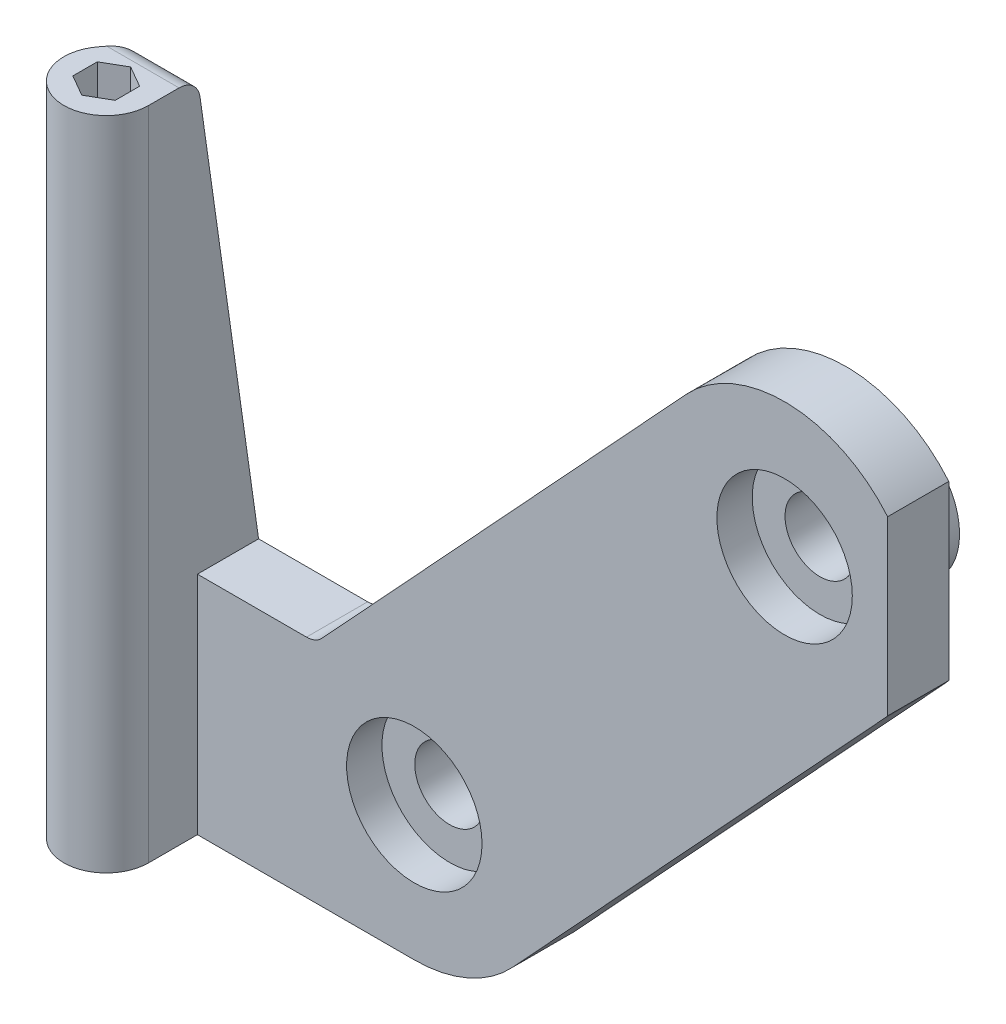
SolidWorks part; units mm, degrees
material "6061-T6 (SS)"
ref_plane "Front Plane" through (0, 0, 0) normal (0, 0, 1) x (1, 0, 0)
ref_plane "Top Plane" through (0, 0, 0) normal (0, 1, 0) x (1, 0, 0)
ref_plane "Right Plane" through (0, 0, 0) normal (1, 0, 0) x (0, 0, -1)
ref_axis "Axis1" through (0, 0, 55) along (0, 0, -1)
sketch "Sketch1" plane through (0, 0, 0) normal (0, 0, 1) x (1, 0, 0)
  line L0 (0, 0) -> (0, 18.9) construction
  line L1 (0, 18.9) -> (17.5, 18.9) construction
  line L2 (4.6594, -4.3142) -> (22.1594, 14.5858)
  line L3 (-4.6594, 4.3142) -> (12.8406, 23.2142)
  arc A0 (-4.6594, 4.3142) -> (4.6594, -4.3142) centre (0, 0) ccw
  arc A1 (22.1594, 14.5858) -> (12.8406, 23.2142) centre (17.5, 18.9) ccw
  dimension "D1" = 12.7
  dimension "D2" = 17.5
  dimension "D3" = 18.9
extrude "Boss-Extrude1" add sketch "Sketch1" along normal mid plane 2.89
sketch "Sketch2" plane through (0, 0, 1.445) normal (0, 0, 1) x (1, 0, 0)
  circle A0 centre (0, 0) radius 3.2
  circle A1 centre (17.5, 18.9) radius 3.2
  dimension "D1" = 6.4
extrude "Cut-Extrude1" cut sketch "Sketch2" against normal blind 1.67
sketch "Sketch3" plane through (0, 0, -0.225) normal (0, 0, 1) x (1, 0, 0)
  circle A0 centre (0, 0) radius 3.2 construction
  circle A1 centre (0, 0) radius 3.2
  circle A2 centre (17.5, 18.9) radius 3.2 construction
  circle A3 centre (17.5, 18.9) radius 3.2
extrude "Boss-Extrude2" add sketch "Sketch3" against normal blind 3.4
sketch "Sketch5" plane through (0, 0, 1.445) normal (0, 0, 1) x (1, 0, 0)
  line L0 (22.37, 14.825) -> (22.37, 22.975)
  arc A0 (22.1594, 14.5858) -> (12.8406, 23.2142) centre (17.5, 18.9) ccw construction
  arc A1 (22.37, 14.825) -> (22.37, 22.975) centre (17.5, 18.9) ccw
  point P7 (22.37, 14.8132)
  point P10 (0, 0)
  point P11 (0, 0)
  point P12 (0, 0)
  dimension "D1" = 4.87
extrude "Cut-Extrude3" cut sketch "Sketch5" against normal through all
sketch "Sketch6" plane through (0, 0, -0.225) normal (0, 0, 1) x (1, 0, 0)
  circle A0 centre (0, 0) radius 1.65
  circle A1 centre (17.5, 18.9) radius 1.65
  dimension "D1" = 3.3
extrude "Cut-Extrude4" cut sketch "Sketch6" against normal through all
sketch "Sketch7" plane through (0, 0, 1.445) normal (0, 0, 1) x (1, 0, 0)
  line L0 (-4.6594, 4.3142) -> (-13, 4.3142)
  line L1 (-13, 4.3142) -> (-13, -6.35)
  line L2 (0, -6.35) -> (-13, -6.35)
  line L6 (22.37, 14.825) -> (22.37, 22.975)
  line L7 (12.8406, 23.2142) -> (-4.6594, 4.3142)
  line L8 (4.6594, -4.3142) -> (22.1594, 14.5858)
  arc A0 (-4.6594, 4.3142) -> (4.6594, -4.3142) centre (0, 0) ccw construction
  arc A4 (22.37, 22.975) -> (12.8406, 23.2142) centre (17.5, 18.9) ccw
  arc A5 (-4.6594, 4.3142) -> (4.6594, -4.3142) centre (0, 0) ccw
  arc A6 (22.1594, 14.5858) -> (22.37, 14.825) centre (17.5, 18.9) ccw
  arc A8 (-4.6594, 4.3142) -> (0, -6.35) centre (0, 0) ccw
  point P3 (-21.4195, -6.1651)
  point P4 (0, -6.35)
  point P6 (-21.4931, -6.509)
  point P12 (0, 0)
  dimension "D1" = 13
  dimension "D2" = 0
extrude "Boss-Extrude3" add sketch "Sketch7" against normal up to surface (2.89 mm away) up to face at (20.7, 18.9, -1.445)
sketch "Sketch8" plane through (0, -6.35, 0) normal (0, -1, 0) x (1, 0, 0)
  line L0 (-13, -1.445) -> (-13, 1.445) construction
  line L1 (-11.5, 3.322) -> (-11.5, 4.188) construction
  line L2 (-11.5, 4.188) -> (-12.25, 4.621) construction
  line L3 (-12.25, 4.621) -> (-13, 4.188) construction
  line L4 (-13, 4.188) -> (-13, 3.322) construction
  line L5 (-13, 3.322) -> (-12.25, 2.889) construction
  line L6 (-12.25, 2.889) -> (-11.5, 3.322) construction
  line L7 (-13, 1.445) -> (0, 1.445) construction
  line L8 (-13, 1.445) -> (-13.8378, 2.5389)
  line L9 (-10.25, 3.755) -> (-10.25, 1.445)
  line L11 (-12.25, 2.6003) -> (-11.25, 3.1776)
  line L12 (-11.25, 3.1776) -> (-11.25, 4.3324)
  line L13 (-11.25, 4.3324) -> (-12.25, 4.9097)
  line L14 (-12.25, 4.9097) -> (-13.25, 4.3324)
  line L15 (-13.25, 4.3324) -> (-13.25, 3.1776)
  line L16 (-13.25, 3.1776) -> (-12.25, 2.6003)
  circle A0 centre (-12.25, 3.755) radius 0.75 construction
  circle A1 centre (-12.25, 3.755) radius 1 construction
  arc A2 (-10.25, 3.755) -> (-13.8378, 2.5389) centre (-12.25, 3.755) ccw
  circle A3 centre (-12.25, 3.755) radius 2 construction
  circle A4 centre (-12.25, 3.755) radius 1 construction
  line M10 (0, 1.445) -> (-13, 1.445)
  dimension "D1" = 1.5
  dimension "D5" = 2
  dimension "D3" = 2.31
  dimension "D4" = 1
extrude "Boss-Extrude4" add sketch "Sketch8" against normal blind 31 contours L9 A2 L8 A1 M10 region at (-13.3722, -6.35, 2.0277)
sketch "Sketch10" plane through (-13, 0, 0) normal (-1, 0, 0) x (0, 0, 1)
  line L0 (-1.445, 4.3142) -> (1.445, 24.65)
  line L1 (1.445, 24.65) -> (1.445, 4.3142)
  line L2 (1.445, 4.3142) -> (-1.445, 4.3142)
extrude "Boss-Extrude5" add sketch "Sketch10" against normal up to surface (2.75 mm away) up to face at (-10.25, 8.1828, 2.369)
fillet "Fillet2" radius 1 2 edges at (-11.625, 24.65, 1.445) (-4.6594, 4.3142, 0)
